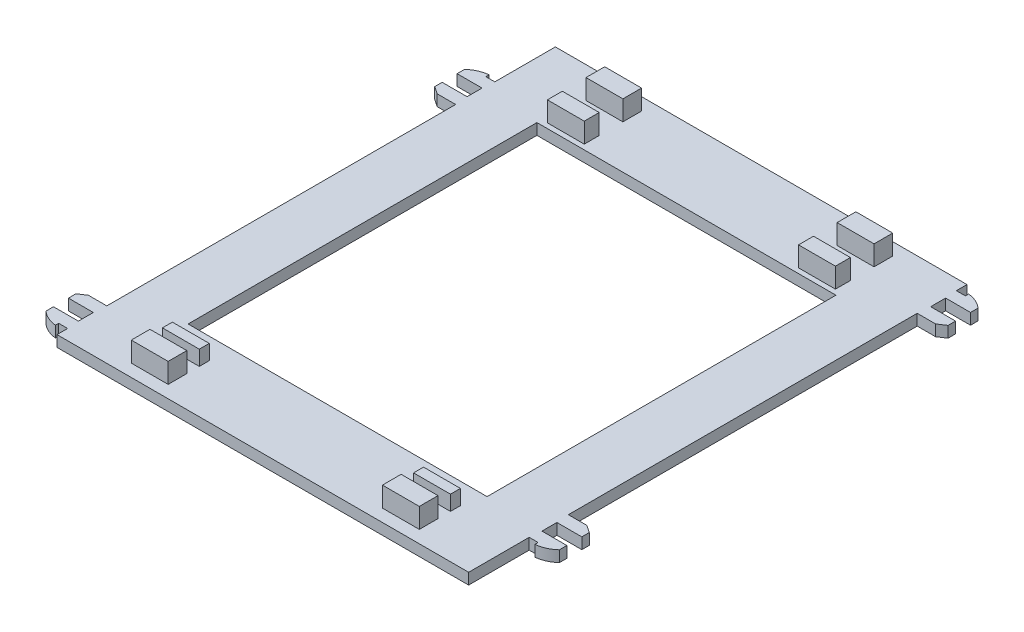
SolidWorks part; units mm, degrees
ref_plane "Front" through (0, 0, 0) normal (0, 0, 1) x (1, 0, 0)
ref_plane "Top" through (0, 0, 0) normal (0, 1, 0) x (1, 0, 0)
ref_plane "Right" through (0, 0, 0) normal (1, 0, 0) x (0, 0, -1)
sketch "Sketch1" plane through (0, 0, 0) normal (0, 1, 0) x (1, 0, 0)
  line L0 (43.1, 45.51) -> (46.5, 45.51)
  line L1 (-41.3, 50) -> (41.3, 50)
  line L2 (-41.3, 50) -> (-41.3, -50)
  line L3 (-41.3, -50) -> (41.3, -50)
  line L4 (41.3, 50) -> (41.3, -50)
  line L5 (-41.3, 50) -> (41.3, -50) construction
  line L6 (-41.3, -50) -> (41.3, 50) construction
  line L7 (41.3, 47.87) -> (43.1, 47.87)
  line L8 (41.3, 47.87) -> (41.3, 45.51)
  line L9 (41.3, 45.51) -> (43.1, 45.51)
  line L10 (43.1, 47.87) -> (43.1, 45.51)
  line L11 (46.5, 45.51) -> (46.5, 47.01)
  line L12 (43.1, 47.87) -> (43.1, 48.52)
  line L13 (41.3, 45.51) -> (41.5, 45.51)
  line L14 (41.3, 45.51) -> (41.3, 42.51)
  line L15 (41.3, 42.51) -> (41.5, 42.51)
  line L16 (41.5, 45.51) -> (41.5, 42.51)
  line L17 (41.5, 42.51) -> (46.5, 42.51)
  line L18 (46.5, 42.51) -> (46.5, 41.01)
  line L19 (46.5, 41.01) -> (45, 40.01)
  line L20 (45, 40.01) -> (41.3, 40.01)
  line L21 (41.3, 5.01) -> (60.4529, 5.01) construction
  line L22 (41.5, -32.49) -> (46.5, -32.49)
  line L23 (46.5, -32.49) -> (46.5, -30.99)
  line L24 (46.5, -30.99) -> (45, -29.99)
  line L25 (45, -29.99) -> (41.3, -29.99)
  line L26 (43.1, -37.85) -> (43.1, -38.5)
  line L27 (46.5, -35.49) -> (46.5, -36.99)
  line L28 (43.1, -35.49) -> (46.5, -35.49)
  line L29 (41.3, -35.49) -> (43.1, -35.49)
  line L30 (43.1, -37.85) -> (43.1, -35.49)
  line L31 (41.3, -37.85) -> (43.1, -37.85)
  line L32 (41.3, -37.85) -> (41.3, -35.49)
  line L33 (41.3, -32.49) -> (41.5, -32.49)
  line L34 (41.5, -35.49) -> (41.5, -32.49)
  line L35 (41.3, -35.49) -> (41.5, -35.49)
  line L36 (41.3, -35.49) -> (41.3, -32.49)
  line L37 (0, 36.7793) -> (0, -23.6766) construction
  line L38 (-41.3, -5.01) -> (-64.7336, -5.01) construction
  line L39 (-45, -40.01) -> (-41.3, -40.01)
  line L40 (-46.5, -41.01) -> (-45, -40.01)
  line L41 (-46.5, -42.51) -> (-46.5, -41.01)
  line L42 (-41.5, -42.51) -> (-46.5, -42.51)
  line L43 (-41.5, -45.51) -> (-41.5, -42.51)
  line L44 (-41.3, -45.51) -> (-46.5, -45.51)
  line L45 (-43.1, -47.87) -> (-41.3, -47.87)
  line L46 (-43.1, -47.87) -> (-43.1, -48.52)
  line L47 (-46.5, -45.51) -> (-46.5, -47.01)
  line L59 (-41.3, 47.87) -> (-41.3, 45.51)
  line L60 (-41.3, 47.87) -> (-41.3, 37.87) construction
  line L61 (-43.1, 37.85) -> (-41.3, 37.85)
  line L62 (-43.1, 37.85) -> (-43.1, 38.5)
  line L63 (-41.3, 35.49) -> (-46.5, 35.49)
  line L64 (-46.5, 35.49) -> (-46.5, 36.99)
  line L65 (-41.5, 35.49) -> (-41.5, 32.49)
  line L66 (-41.5, 32.49) -> (-46.5, 32.49)
  line L67 (-46.5, 32.49) -> (-46.5, 30.99)
  line L68 (-46.5, 30.99) -> (-45, 29.99)
  line L69 (-45, 29.99) -> (-41.3, 29.99)
  arc A0 (43.1, 48.52) -> (46.5, 47.01) centre (42.5287, 42.6507) cw
  arc A1 (43.1, -38.5) -> (46.5, -36.99) centre (42.5287, -32.6307) ccw
  arc A2 (-46.5, -47.01) -> (-43.1, -48.52) centre (-42.5287, -42.6507) ccw
  arc A4 (-46.5, 36.99) -> (-43.1, 38.5) centre (-42.5287, 32.6307) cw
  point P0 (0, 0)
  dimension "D9" = 0.65
  dimension "D10" = 5.897
  dimension "D25" = 5.897
  dimension "D1" = 82.6
  dimension "D2" = 100
  dimension "D3" = 2.13
  dimension "D4" = 2.36
  dimension "D5" = 1.8
  dimension "D6" = 0.2
  dimension "D7" = 5.2
  dimension "D8" = 1.5
  dimension "D11" = 3
  dimension "D12" = 1.5
  dimension "D13" = 3.7
  dimension "D14" = 2.5
  dimension "D15" = 5.2
  dimension "D16" = 35
  dimension "D17" = 10
  dimension "D18" = 5.2
  dimension "D19" = 1.8
  dimension "D20" = 1.5
  dimension "D21" = 12.15
  dimension "D22" = 2.36
  dimension "D23" = 0.2
  dimension "D24" = 0.65
  dimension "D26" = 1.5
  dimension "D27" = 2.5
  dimension "D28" = 3.7
  dimension "D29" = 5
  dimension "D30" = 3
  dimension "D31" = 35
  dimension "D32" = 2.13
extrude "Boss-Extrude1" add sketch "Sketch1" along normal blind 2.23 contours L26 A1 L27 L28 L30 | L4 L31 L30 L29 | L4 L33 L22 L23 L24 L25 | L29 L34 L33 L4 | L4 L1 L2 L3 | L20 L19 L18 L17 L15 L4 | L16 L9 L4 L15 | L10 L7 L4 L9 | A0 L12 L10 L0 L11 | L47 A2 L46 L45 L2 L44 | L44 L2 L39 L40 L41 L42 L43 | L68 L69 L2 L63 L65 L66 L67 | A4 L64 L63 L2 L61 L62 region at (44.6316, 0, -46.7862) region at (42.2, 0, -46.69) region at (41.4, 0, -44.01) region at (0, 0, 0) region at (43.7714, 0, -41.3161) region at (43.7714, 0, 31.2961) region at (41.4, 0, 33.99) region at (42.2, 0, 36.67) region at (-43.816, 0, -36.734) region at (-43.6607, 0, -31.4219) region at (44.6316, 0, 36.7662) region at (-43.6607, 0, 41.4419) region at (-43.816, 0, 46.754)
sketch "Sketch2" plane through (0, 2.23, 0) normal (0, 1, 0) x (1, 0, 0)
  line L0 (-41.3, -50) -> (41.3, -50) construction
  line L1 (-21.5, -43.75) -> (-28.9, -43.75)
  line L2 (-21.5, -43.75) -> (-21.5, -47.5)
  line L3 (-21.5, -47.5) -> (-28.9, -47.5)
  line L4 (-28.9, -43.75) -> (-28.9, -47.5)
  line L5 (-41.5, -45.51) -> (-41.5, -42.51) construction
  line L6 (0, -50) -> (0, -10.7982) construction
  line L7 (21.5, -43.75) -> (21.5, -47.5)
  line L8 (21.5, -47.5) -> (28.9, -47.5)
  line L9 (28.9, -43.75) -> (28.9, -47.5)
  line L10 (21.5, -43.75) -> (28.9, -43.75)
  line L11 (-26.6786, 0) -> (25.6107, 0) construction
  line L12 (21.5, 47.5) -> (28.9, 47.5)
  line L13 (28.9, 43.75) -> (28.9, 47.5)
  line L14 (21.5, 43.75) -> (28.9, 43.75)
  line L15 (21.5, 43.75) -> (21.5, 47.5)
  line L16 (-21.5, 43.75) -> (-21.5, 47.5)
  line L17 (-21.5, 47.5) -> (-28.9, 47.5)
  line L18 (-28.9, 43.75) -> (-28.9, 47.5)
  line L19 (-21.5, 43.75) -> (-28.9, 43.75)
  line L20 (-28.9, 36) -> (-28.9, 39)
  line L21 (-28.9, -36) -> (-21.5, -36)
  line L22 (-28.9, -36) -> (-28.9, -39)
  line L23 (-28.9, -39) -> (-21.5, -39)
  line L24 (-21.5, -36) -> (-21.5, -39)
  line L25 (-28.9, 36) -> (-21.5, 36)
  line L26 (-21.5, 36) -> (-21.5, 39)
  line L27 (-28.9, 39) -> (-21.5, 39)
  line L28 (28.9, 36) -> (28.9, 39)
  line L29 (28.9, 36) -> (21.5, 36)
  line L30 (21.5, 36) -> (21.5, 39)
  line L31 (28.9, 39) -> (21.5, 39)
  line L32 (21.5, -36) -> (21.5, -39)
  line L33 (28.9, -36) -> (21.5, -36)
  line L34 (28.9, -36) -> (28.9, -39)
  line L35 (28.9, -39) -> (21.5, -39)
  dimension "D1" = 2.5
  dimension "D2" = 12.6
  dimension "D3" = 7.4
  dimension "D4" = 3.75
  dimension "D5" = 4.75
  dimension "D6" = 3
  dimension "D7" = 7.4
extrude "Boss-Extrude2" add sketch "Sketch2" along normal blind 4 contours L2 L1 L4 L3 | L7 L8 L9 L10 | L28 L31 L30 L29 | L20 L27 L26 L25 | L16 L17 L18 L19 | L12 L13 L14 L15
sketch "Sketch3" plane through (0, 2.23, 0) normal (0, 1, 0) x (1, 0, 0)
  line L1 (-30, 35) -> (30, 35)
  line L2 (-30, 35) -> (-30, -35)
  line L3 (-30, -35) -> (30, -35)
  line L4 (30, 35) -> (30, -35)
  line L5 (-30, 35) -> (30, -35) construction
  line L6 (-30, -35) -> (30, 35) construction
  point P0 (0, 0)
  dimension "D1" = 70
  dimension "D2" = 60
extrude "Cut-Extrude1" cut sketch "Sketch3" against normal blind 10
sketch "Sketch4" plane through (0, 0, 0) normal (0, -1, 0) x (1, 0, 0)
  line L0 (41.3, -40) -> (-41.3, -40) construction
  line L1 (41.3, -40.01) -> (41.3, 29.99) construction
  line L2 (-41.3, -29.99) -> (-41.3, 40.01) construction
  line L3 (-41.3, -50) -> (41.3, -50) construction
  text T0 "+Z↑"
  dimension "D1" = 10
extrude "Cut-Extrude2" cut sketch "Sketch4" against normal blind 0.5
sketch "Sketch5" plane through (0, 2.23, 0) normal (0, 1, 0) x (1, 0, 0)
  line L0 (-28.9, -43.75) -> (-28.9, -47.5) construction
  line L1 (-28.9, -41.25) -> (-21.5, -41.25)
  line L2 (-28.9, -41.25) -> (-28.9, -39.25)
  line L3 (-28.9, -39.25) -> (-21.5, -39.25)
  line L4 (-21.5, -41.25) -> (-21.5, -39.25)
  line L5 (21.5, -39.25) -> (28.9, -39.25)
  line L6 (21.5, -39.25) -> (21.5, -41.25)
  line L7 (21.5, -41.25) -> (28.9, -41.25)
  line L8 (28.9, -39.25) -> (28.9, -41.25)
  line L9 (-21.5, -43.75) -> (-21.5, -47.5) construction
  line L10 (28.9, -43.75) -> (28.9, -47.5) construction
  line L11 (21.5, -43.75) -> (21.5, -47.5) construction
  line L12 (-21.5, -39.25) -> (21.5, -39.25) construction
  line L13 (-21.5, -43.75) -> (-28.9, -43.75) construction
  line L14 (-21.5, -41.25) -> (21.5, -41.25) construction
  dimension "D1" = 2
  dimension "D2" = 2.5
extrude "Boss-Extrude3" add sketch "Sketch5" along normal blind 3
